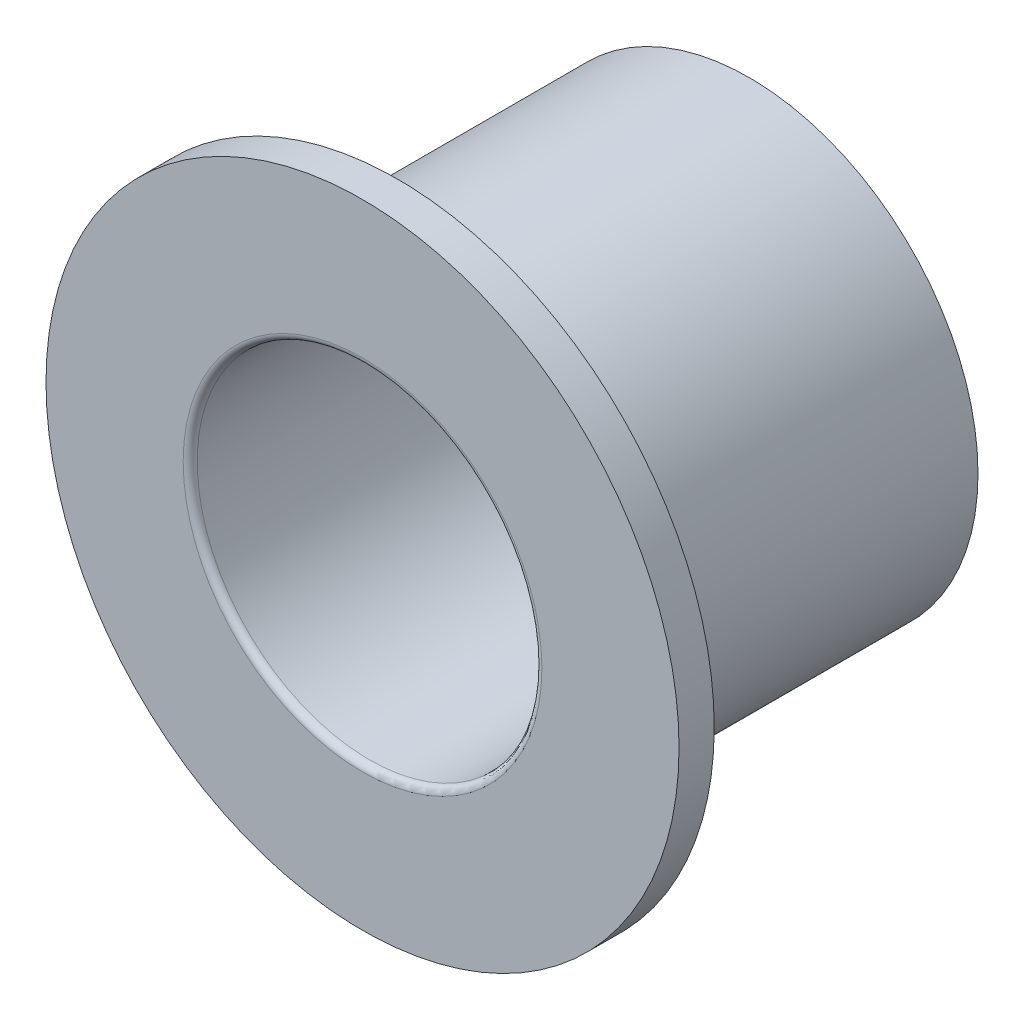
SolidWorks part; units mm, degrees
material "AISI 316 Stainless Steel Sheet (SS)"
ref_plane "Front Plane" through (0, 0, 0) normal (0, 0, 1) x (1, 0, 0)
ref_plane "Top Plane" through (0, 0, 0) normal (0, 1, 0) x (1, 0, 0)
ref_plane "Right Plane" through (0, 0, 0) normal (1, 0, 0) x (0, 0, -1)
sketch "Sketch1" plane through (0, 0, 0) normal (0, 0, 1) x (1, 0, 0)
  circle A0 centre (0, 0) radius 1.651
  dimension "D1" = 3.302
extrude "Boss-Extrude1" add sketch "Sketch1" along normal blind 2.54 contours A0
sketch "Sketch2" plane through (0, 0, 2.54) normal (0, 0, 1) x (1, 0, 0)
  circle A0 centre (0, 0) radius 2.286
  dimension "D1" = 4.572
extrude "Boss-Extrude2" add sketch "Sketch2" along normal blind 0.254
sketch "Sketch3" plane through (0, 0, 0) normal (0, 0, -1) x (-1, 0, 0)
  circle A0 centre (0, 0) radius 1.2446
  dimension "D1" = 2.4892
extrude "Cut-Extrude3" cut sketch "Sketch3" against normal through all and the other way through all contours A0
sketch "Sketch5" plane through (0, 0, 2.794) normal (0, 0, 1) x (1, 0, 0)
  circle A0 centre (0, 0) radius 1.2446
  dimension "D1" = 2.4892
fillet "Fillet3" radius 0.0508 1 edges at (-1.2446, 0, 2.794)
